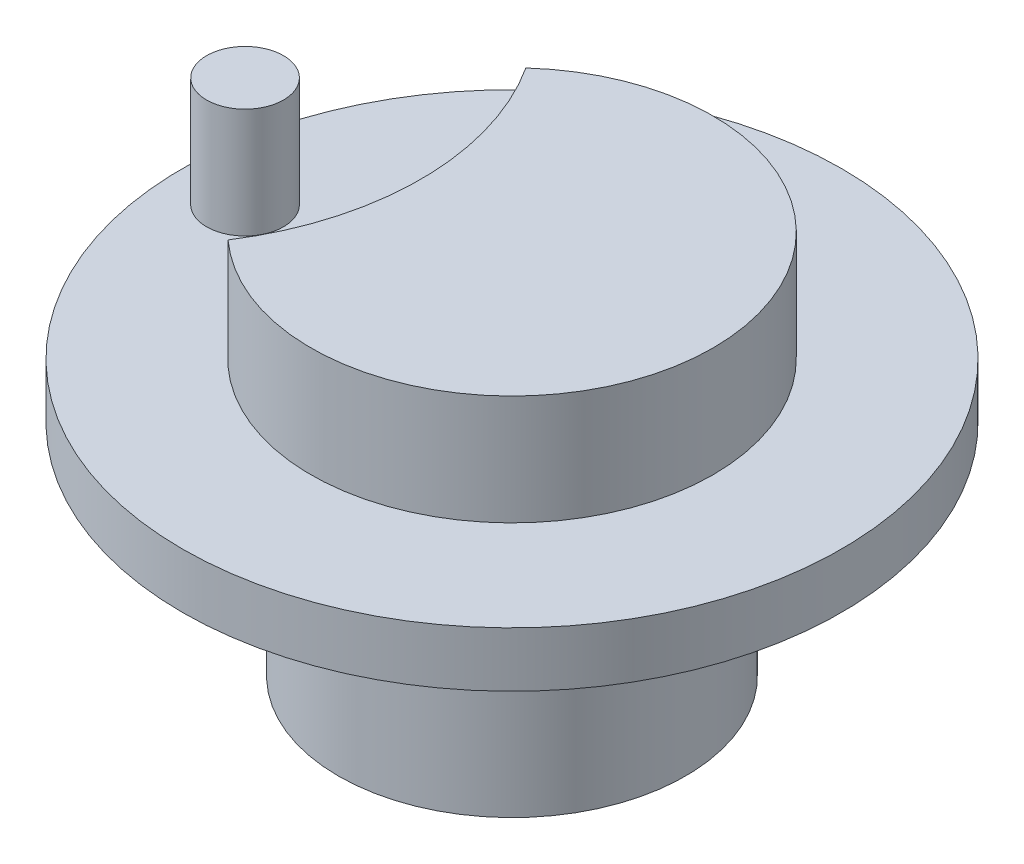
SolidWorks part; units mm, degrees
ref_plane "Alzado" through (0, 0, 0) normal (0, 0, 1) x (1, 0, 0)
ref_plane "Planta" through (0, 0, 0) normal (0, 1, 0) x (1, 0, 0)
ref_plane "Vista lateral" through (0, 0, 0) normal (1, 0, 0) x (0, 0, -1)
sketch "Croquis1" plane through (0, 0, 0) normal (0, 1, 0) x (1, 0, 0)
  line L0 (-55, 0) -> (55, 0) construction
  line L1 (-9.15, 0) -> (9.15, 0) construction
  line L2 (-13.9, -1.75) -> (-10.4, -1.75)
  line L3 (-13.9, -1.75) -> (-13.9, 1.75)
  line L4 (-13.9, 1.75) -> (-10.4, 1.75)
  line L5 (-10.4, -1.75) -> (-10.4, 1.75)
  line L6 (-13.9, -1.75) -> (-10.4, 1.75) construction
  line L7 (-13.9, 1.75) -> (-10.4, -1.75) construction
  line L8 (-4.15, 0) -> (-1.4777, 3.3836) construction
  line L9 (-10.15, 0) -> (-10.15, -4) construction
  line L10 (-10.15, -4) -> (-14.15, -4) construction
  line L11 (-14.15, -4) -> (-14.15, 0) construction
  circle A0 centre (0, 0) radius 9.15
  circle A1 centre (-16.65, 0) radius 12.5
  circle A2 centre (-12.15, 0) radius 1.75
  circle A3 centre (0, 0) radius 15
  point P23 (-12.15, -4)
  dimension "D1" = 18.3
  dimension "D2" = 25
  dimension "D3" = 3.5
  dimension "D4" = 30
  dimension "D6" = 5
  dimension "D7" = 4
  dimension "D8" = 1
  dimension "D9" = 4
extrude "Saliente-Extruir1" add sketch "Croquis1" along normal blind 2.5 contours A3
extrude "Saliente-Extruir2" add sketch "Croquis1<4>" along normal blind 5 from surface contours A1 A0 | A2 region at (-12.15, 0, 0) region at (1.4118, 0, 0) starting at face at (0, 2.5, 15)
sketch "Croquis1<4>" plane through (0, 0, 0) normal (0, 1, 0) x (1, 0, 0) same geometry as "Croquis1"
sketch "Croquis2" plane through (0, 0, 0) normal (0, -1, 0) x (1, 0, 0)
  circle A0 centre (0, 0) radius 7.9
  dimension "D1" = 15.8
extrude "Saliente-Extruir3" add sketch "Croquis2" along normal blind 10
